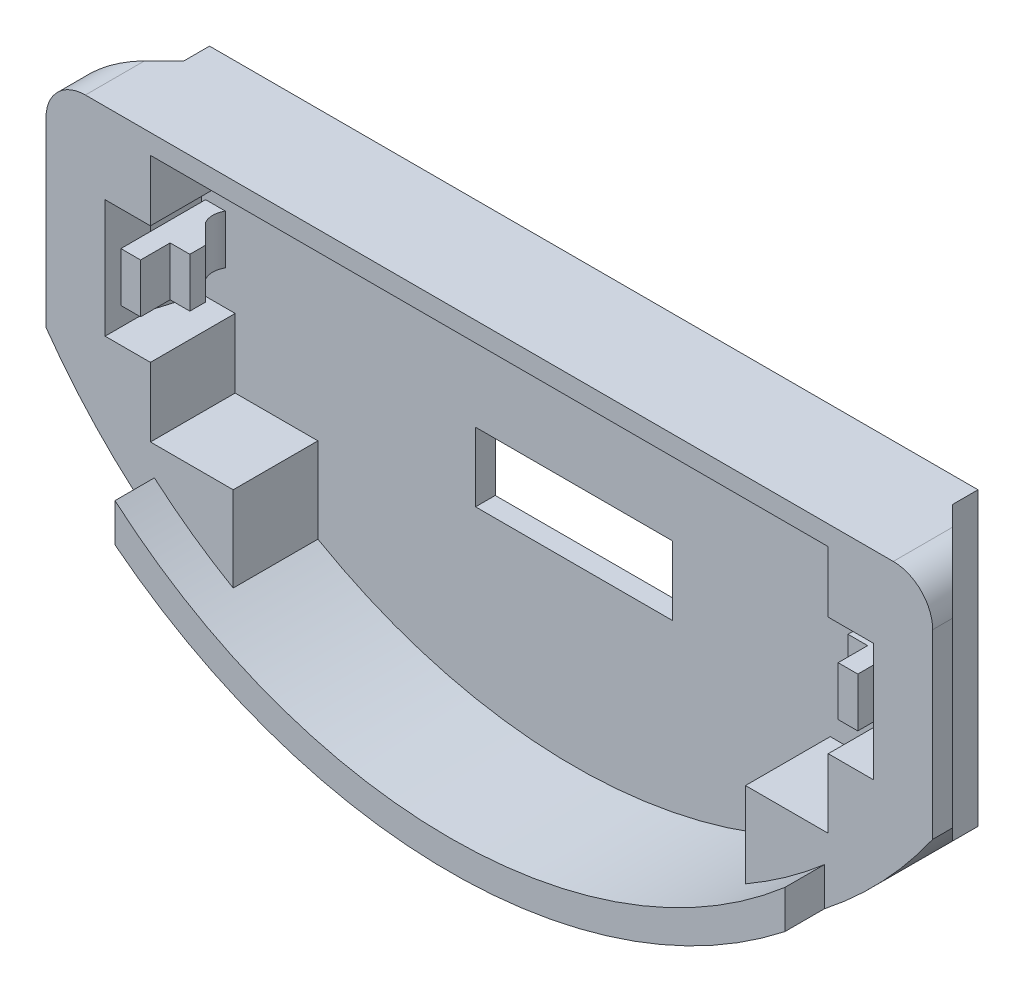
SolidWorks part; units mm, degrees
ref_plane "Front Plane" through (0, 0, 0) normal (0, 0, 1) x (1, 0, 0)
ref_plane "Top Plane" through (0, 0, 0) normal (0, 1, 0) x (1, 0, 0)
ref_plane "Right Plane" through (0, 0, 0) normal (1, 0, 0) x (0, 0, -1)
sketch "Sketch1" plane through (0, 0, 0) normal (0, 0, 1) x (-1, 0, 0)
  line L0 (-22.5, 4.1157) -> (-22.5, -5.1)
  line L2 (22.5, -5.1) -> (22.5, 4.1157)
  line L3 (-17.2, -6.1) -> (-17.2, -3)
  line L4 (-17.2, -6.1) -> (17.2, -6.1)
  line L5 (17.2, -6.1) -> (17.2, -3)
  line L6 (-20.5, -7.1) -> (20.5, -7.1)
  line L11 (-17.2, 6.5) -> (-13, 6.5)
  line L12 (-5, 1.9) -> (5, 1.9)
  line L13 (-5, 1.9) -> (-5, 5.4)
  line L18 (-5, 5.4) -> (5, 5.4)
  line L19 (5, 1.9) -> (5, 5.4)
  line L20 (-5, 1.9) -> (5, 5.4) construction
  line L21 (-5, 5.4) -> (5, 1.9) construction
  line L26 (-16.8, -6.1) -> (16.8, -6.1) construction
  line L27 (-16.8, -6.1) -> (-16.8, 6.1) construction
  line L28 (0, 0) -> (0, 17.0761) construction
  line L29 (-16.8, 6.1) -> (16.8, 6.1) construction
  line L30 (16.8, -6.1) -> (16.8, 6.1) construction
  line L31 (-16.8, -6.1) -> (16.8, 6.1) construction
  line L32 (-16.8, 6.1) -> (16.8, -6.1) construction
  line L33 (-13, 6.5) -> (-13, 10.821)
  line L34 (17.2, 6.5) -> (13, 6.5)
  line L35 (13, 6.5) -> (13, 10.821)
  line L36 (0, 0) -> (-9.1988, 0) construction
  line L37 (-17.2, 3) -> (-19.5, 3)
  line L39 (-17.2, -3) -> (-19.5, -3)
  line L40 (-19.5, 3) -> (-19.5, -3)
  line L41 (17.2, 3) -> (19.5, 3)
  line L43 (17.2, -3) -> (19.5, -3)
  line L44 (19.5, 3) -> (19.5, -3)
  line L45 (-17.2, 3) -> (-17.2, 6.5)
  line L46 (17.2, 3) -> (17.2, 6.5)
  line L48 (-17.7, 1.25) -> (-18.7, 1.25)
  line L49 (-17.7, 1.25) -> (-17.7, -1.25)
  line L50 (-17.7, -1.25) -> (-18.7, -1.25)
  line L51 (-18.7, 1.25) -> (-18.7, -1.25)
  line L52 (17.7, 1.25) -> (18.7, 1.25)
  line L53 (17.7, 1.25) -> (17.7, -1.25)
  line L54 (17.7, -1.25) -> (18.7, -1.25)
  line L55 (18.7, 1.25) -> (18.7, -1.25)
  arc A1 (-13, 10.821) -> (13, 10.821) centre (0, -11.6956) cw
  arc A2 (-22.5, 4.1157) -> (22.5, 4.1157) centre (0, -11.6956) cw
  arc A3 (20.5, -7.1) -> (22.5, -5.1) centre (20.5, -5.1) ccw
  arc A6 (-20.5, -7.1) -> (-22.5, -5.1) centre (-20.5, -5.1) cw
  point P2 (0, 0)
  point P3 (0, 3.65)
  dimension "D3" = 1.5
  dimension "D13" = 2
  dimension "D14" = 26
  dimension "D15" = 11.6956
  dimension "D2" = 6.1
  dimension "D4" = 1
  dimension "D5" = 11.5
  dimension "D6" = 3.5
  dimension "D7" = 10
  dimension "D8" = 33.6
  dimension "D9" = 12.2
  dimension "D10" = 0.7
  dimension "D11" = 45
  dimension "D12" = 0.4
  dimension "D16" = 0.4
  dimension "D17" = 26
  dimension "D18" = 6
  dimension "D19" = 2.3
  dimension "D20" = 2.5
  dimension "D21" = 1
  dimension "D22" = 0.5
extrude "Boss-Extrude1" add sketch "Sketch1" against normal blind 1 contours A6 L6 A3 L2 A2 L0 L33 A1 L35 L34 L46 L41 L44 L43 L5 L4 L3 L39 L40 L37 L45 L11 | L55 L52 L53 L54 | A1 L33 L11 L45 L37 L40 L39 L3 L4 L5 L43 L44 L41 L46 L34 L35 L51 L48 L49 L50 L19 L12 L13 L18 L52 L55 L54 L53 | L48 L51 L50 L49 region at (0, -15.2994, 0) region at (16.7598, 4.55, 0) region at (18.2, 0, 0) region at (-18.2, 0, 0)
extrude "Boss-Extrude2" add sketch "Sketch1<3>" along normal blind 4.3 contours A6 L6 A3 L2 A2 L0 L33 A1 L35 L34 L46 L41 L44 L43 L5 L4 L3 L39 L40 L37 L45 L11 | L55 L52 L53 L54 | L49 L48 L51 L50 region at (0, -15.2994, 0) region at (-18.2, 0, 0)
sketch "Sketch1<3>" plane through (0, 0, 0) normal (0, 0, 1) x (-1, 0, 0) same geometry as "Sketch1"
sketch "Sketch3" plane through (0, -1.25, 0) normal (0, -1, 0) x (1, 0, 0)
  line L0 (-17.7, 2) -> (-17.7, 1)
  line L1 (-17.7, 4.3) -> (-17.7, 0) construction
  line L2 (-17.7, 1) -> (-16.7, 2)
  line L3 (-16.7, 2) -> (-17.7, 2)
  line L5 (17.7, 1) -> (16.7, 2)
  line L8 (-17.7, 1) -> (-17.7, 0)
  line L10 (0, 0) -> (0, 8.8369) construction
  line L11 (17.7, 2) -> (17.7, 1)
  line L12 (-16.7, 2) -> (-17.7, 2)
  line L13 (-16.7, 2) -> (-16.7, 2.8)
  line L14 (-16.7, 2.8) -> (-17.7, 2.8)
  line L15 (-17.7, 2) -> (-17.7, 2.8)
  line L16 (16.7, 2) -> (17.7, 2)
  line L17 (16.7, 2.8) -> (17.7, 2.8)
  line L18 (17.7, 2) -> (17.7, 2.8)
  line L23 (16.7, 2) -> (17.7, 2)
  line L24 (16.7, 2) -> (16.7, 2.8)
  line L25 (17.7, 1) -> (17.7, 0)
  arc A0 (-17.7, 1) -> (-17.7, 0) centre (-16.834, 0.5) ccw
  arc A2 (17.7, 1) -> (17.7, 0) centre (16.834, 0.5) cw
  line M9 (-17.7, 0) -> (-17.7, 4.3)
  dimension "D4" = 1
  dimension "D1" = 1
  dimension "D2" = 1
  dimension "D3" = 1
  dimension "D5" = 0.8
extrude "Cut-Extrude1" cut sketch "Sketch3" against normal up to next contours A0 M9 | L25 A2 region at (-17.7539, -1.25, 0.5)
sketch "Sketch4" plane through (0, 7.1, 0) normal (0, 1, 0) x (1, 0, 0)
  line L0 (19.5, 1) -> (19.5, -0.3)
  line L1 (19.5, 1) -> (22.5, 1)
  line L2 (22.5, 1) -> (22.5, -3.3)
  line L3 (20.5, 1) -> (-20.5, 1) construction
  line L4 (22.5, 1) -> (22.5, -4.3) construction
  line L5 (19.5, -0.3) -> (22.5, -3.3)
  line L9 (20.5, -4.3) -> (-20.5, -4.3) construction
  line L10 (0, 0) -> (0, 14.5506) construction
  line L11 (-19.5, -0.3) -> (-22.5, -3.3)
  line L12 (-22.5, 1) -> (-22.5, -3.3)
  line L13 (-19.5, 1) -> (-22.5, 1)
  line L14 (-19.5, 1) -> (-19.5, -0.3)
  dimension "D1" = 45
  dimension "D2" = 1
  dimension "D3" = 3
extrude "Cut-Extrude2" cut sketch "Sketch4" against normal through all
sketch "Sketch5" plane through (0, 0, 4.3) normal (0, 0, 1) x (1, 0, 0)
  line L0 (17, -7.9767) -> (17, -9.9203)
  line L1 (-17, -9.9203) -> (-17, -7.9767)
  line L2 (0, 5.3141) -> (0, -21.8072) construction
  arc A0 (-17, -9.9203) -> (17, -9.9203) centre (0, 11.6956) ccw
  arc A1 (-22.5, -4.1157) -> (22.5, -4.1157) centre (0, 11.6956) ccw construction
  arc A2 (-17, -7.9767) -> (17, -7.9767) centre (0, 11.6956) ccw
  arc A3 (-13, -10.821) -> (13, -10.821) centre (0, 11.6956) ccw construction
  arc A4 (-13, -10.821) -> (13, -10.821) centre (0, 11.6956) ccw construction
  dimension "D1" = 34
extrude "Boss-Extrude4" add sketch "Sketch5" along normal blind 2
extrude "Boss-Extrude5" add sketch "Sketch3<5>" against normal up to surface (2.5 mm away) contours L24 L16 L18 L17 | L16 L5 L11 | L13 L14 L3 M9 | L2 L3 M9 region at (-17.3667, -1.25, 1.6667) region at (-17.2, -1.25, 2.4) region at (17.3667, -1.25, 1.6667) region at (17.2, -1.25, 2.4) up to face at (-18.1268, 1.25, 1.92)
sketch "Sketch3<5>" plane through (0, -1.25, 0) normal (0, -1, 0) x (1, 0, 0) same geometry as "Sketch3"
sketch "Sketch6" plane through (0, 3, 0) normal (0, -1, 0) x (1, 0, 0)
  line L0 (19.5, 2) -> (19.5, 0)
  line L1 (19.5, 4.3) -> (19.5, 0.3) construction
  line L2 (19.5, 0) -> (18.9, 0)
  line L3 (17.2, 0) -> (19.5, 0) construction
  line L4 (18.9, 0) -> (19.5, 2)
  line L5 (0, 0) -> (0, 14.6399) construction
  line L6 (-18.9, 0) -> (-19.5, 2)
  line L7 (-19.5, 0) -> (-18.9, 0)
  line L8 (-19.5, 2) -> (-19.5, 0)
  dimension "D1" = 0.6
  dimension "D2" = 2
extrude "Boss-Extrude6" add sketch "Sketch6" along normal up to next
